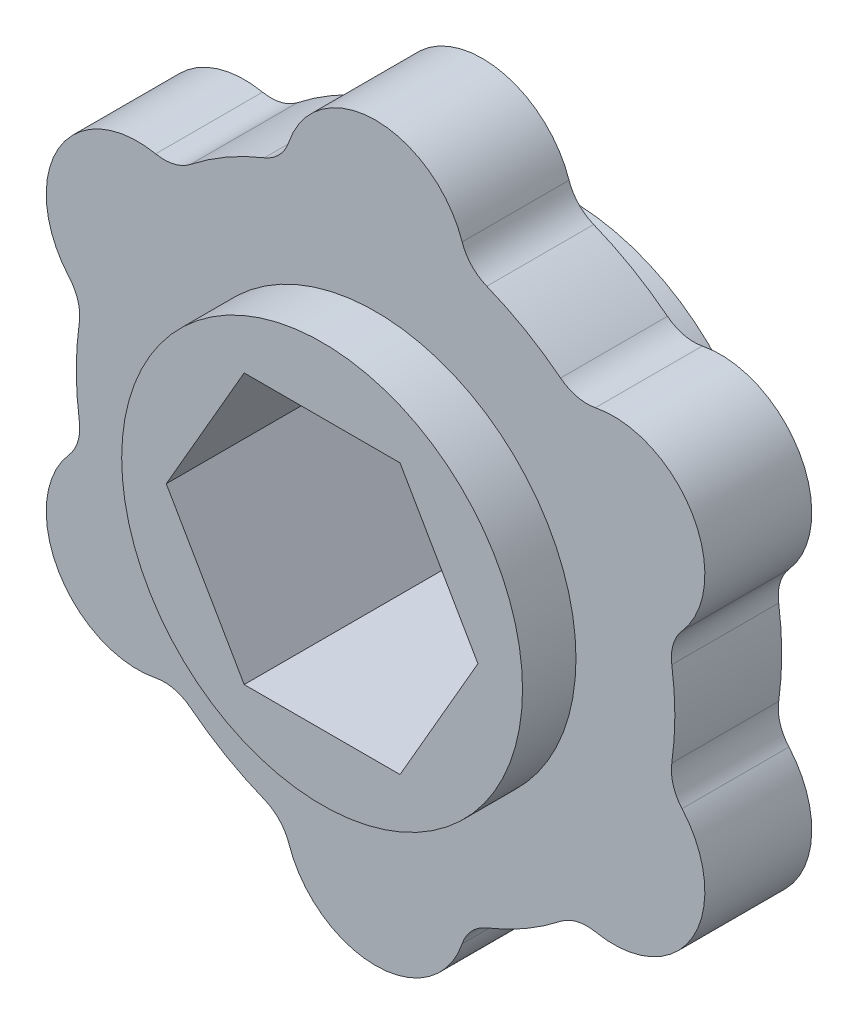
SolidWorks part; units mm, degrees
material "PET"
ref_plane "Front Plane" through (0, 0, 0) normal (0, 0, 1) x (1, 0, 0)
ref_plane "Top Plane" through (0, 0, 0) normal (0, 1, 0) x (1, 0, 0)
ref_plane "Right Plane" through (0, 0, 0) normal (1, 0, 0) x (0, 0, -1)
sketch "Sketch5" plane through (0, 0, 0) normal (0, 0, 1) x (1, 0, 0)
  line L0 (0, 0) -> (0, 13.0556) construction
  circle A0 centre (0, 0) radius 14.224
  circle A1 centre (0, 0) radius 17.399 construction
  arc A2 (-4.3147, 13.5538) -> (4.3147, 13.5538) centre (0, 13.0556) cw
  arc A3 (9.5806, 10.5136) -> (13.8953, 3.0402) centre (11.3065, 6.5278) cw
  arc A4 (13.8953, -3.0402) -> (9.5806, -10.5136) centre (11.3065, -6.5278) cw
  arc A5 (4.3147, -13.5538) -> (-4.3147, -13.5538) centre (0, -13.0556) cw
  arc A6 (-9.5806, -10.5136) -> (-13.8953, -3.0402) centre (-11.3065, -6.5278) cw
  arc A7 (-13.8953, 3.0402) -> (-9.5806, 10.5136) centre (-11.3065, 6.5278) cw
  point P24 (0, 0)
  dimension "D1" = 28.448
  dimension "D2" = 34.798
  dimension "D3" = 4.3434
  dimension "D4" = 6
extrude "Boss-Extrude2" add sketch "Sketch5" along normal blind 5.08 contours A7 A0 | A2 A0 | A3 A0 | A4 A0 | A5 A0 | A6 A0 | A0 region at (13.3495, 7.7073, 0) region at (13.3495, -7.7073, 0) region at (0, 15.4147, 0) region at (0, -15.4147, 0) region at (-13.3495, 7.7073, 0) region at (-13.3495, -7.7073, 0)
fillet "Fillet1" radius 2.032 12 edges at (-9.5806, 10.5136, 2.54) (-4.3147, 13.5538, 2.54) (4.3147, 13.5538, 2.54) (9.5806, 10.5136, 2.54) (13.8953, 3.0402, 2.54) (13.8953, -3.0402, 2.54) (9.5806, -10.5136, 2.54) (4.3147, -13.5538, 2.54) (-4.3147, -13.5538, 2.54) (-9.5806, -10.5136, 2.54) (-13.8953, -3.0402, 2.54) (-13.8953, 3.0402, 2.54)
sketch "Sketch6" plane through (0, 0, 5.08) normal (0, 0, 1) x (1, 0, 0)
  line L1 (7.4057, 0) -> (3.7028, 6.4135)
  line L2 (3.7028, 6.4135) -> (-3.7028, 6.4135)
  line L3 (-3.7028, 6.4135) -> (-7.4057, 0)
  line L4 (-7.4057, 0) -> (-3.7028, -6.4135)
  line L5 (-3.7028, -6.4135) -> (3.7028, -6.4135)
  line L6 (3.7028, -6.4135) -> (7.4057, 0)
  circle A0 centre (0, 0) radius 6.4135 construction
  dimension "D1" = 12.827
extrude "Cut-Extrude1" cut sketch "Sketch6" against normal through all
sketch "Sketch7" plane through (0, 0, 0) normal (0, 0, -1) x (-1, 0, 0)
  line L0 (-7.4057, 0) -> (-3.7028, 6.4135) construction
  line L1 (-3.7028, -6.4135) -> (-7.4057, 0) construction
  line L2 (3.7028, -6.4135) -> (-3.7028, -6.4135) construction
  line L3 (7.4057, 0) -> (3.7028, -6.4135) construction
  line L4 (3.7028, 6.4135) -> (7.4057, 0) construction
  line L5 (-3.7028, 6.4135) -> (3.7028, 6.4135) construction
  line L6 (-7.4057, 0) -> (-3.7028, 6.4135)
  line L7 (-3.7028, -6.4135) -> (-7.4057, 0)
  line L8 (3.7028, -6.4135) -> (-3.7028, -6.4135)
  line L9 (7.4057, 0) -> (3.7028, -6.4135)
  line L10 (3.7028, 6.4135) -> (7.4057, 0)
  line L11 (-3.7028, 6.4135) -> (3.7028, 6.4135)
  circle A0 centre (0, 0) radius 9.525
  dimension "D1" = 19.05
extrude "Boss-Extrude3" add sketch "Sketch7" along normal blind 4.143 and the other way blind 7.62
